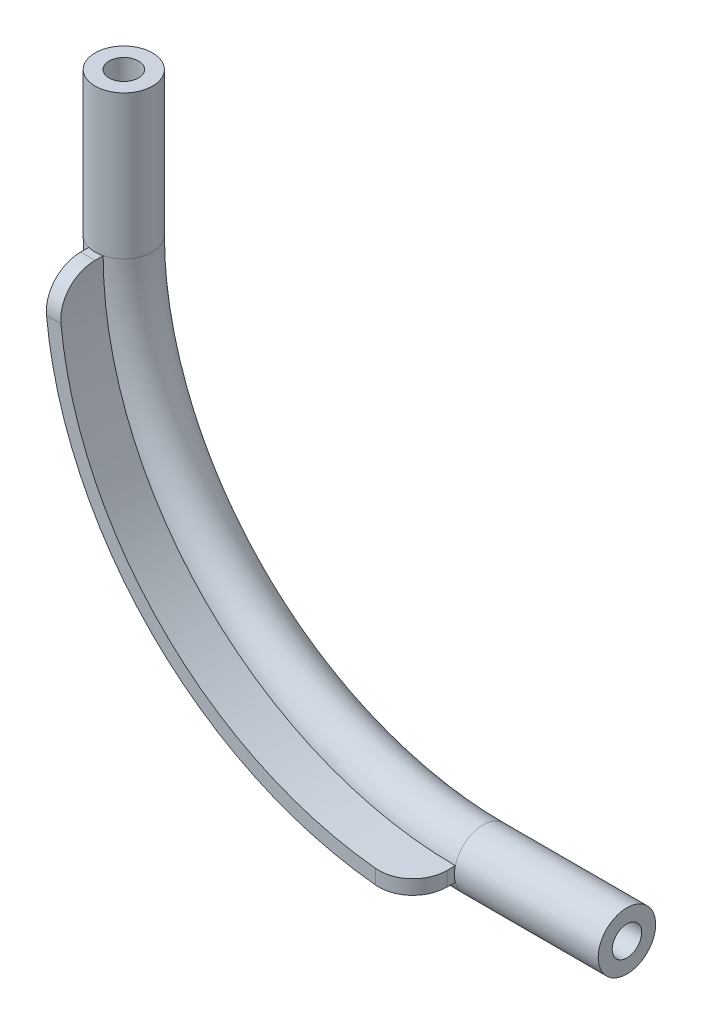
SolidWorks part; units mm, degrees
ref_plane "前基準面" through (0, 0, 0) normal (0, 0, 1) x (1, 0, 0)
ref_plane "上基準面" through (0, 0, 0) normal (0, 1, 0) x (1, 0, 0)
ref_plane "右基準面" through (0, 0, 0) normal (1, 0, 0) x (0, 0, -1)
sketch "草圖4" plane through (0, 0, 0) normal (0, 1, 0) x (1, 0, 0)
  line L0 (0, 3.4749) -> (0, -3.49) construction
  line L1 (0, -3.8307) -> (0, 3.8307) construction
  line L2 (-55, 0) -> (55, 0) construction
  circle A0 centre (-50, 0) radius 4
  dimension "D1" = 50
  dimension "D2" = 8
revolve "旋轉1" add sketch "草圖4" angle 90 about L0
sketch "草圖5" plane through (0, 0, 0) normal (1, 0, 0) x (0, 0, -1)
  circle A0 centre (0, -50) radius 4 construction
  circle A1 centre (0, -50) radius 4
  circle A2 centre (0, -50) radius 2.05
  dimension "D1" = 4.1
extrude "填料-伸長4" add sketch "草圖5" along normal blind 20 contours A1 | A2
sketch "草圖6" plane through (0, 0, 0) normal (0, 1, 0) x (1, 0, 0)
  circle A0 centre (-50, 0) radius 4 construction
  circle A1 centre (-50, 0) radius 4
  circle A2 centre (-50, 0) radius 2.05
  dimension "D1" = 4.1
extrude "填料-伸長5" add sketch "草圖6" along normal blind 20
sketch "草圖7" plane through (0, 0, 0) normal (0, 0, 1) x (1, 0, 0)
  line L0 (10.0499, -50) -> (-4.9615, -50) construction
  line L2 (-3.7268, -49) -> (6.7893, -49) construction
  line L3 (-3.7268, -51) -> (6.7893, -51) construction
  line L4 (-49, 0) -> (-51, 0)
  line L5 (0, -49) -> (0, -51)
  arc A0 (-49, 0) -> (0, -49) centre (0, 0) ccw
  arc A1 (-51, 0) -> (0, -51) centre (0, 0) ccw
  dimension "D1" = 1
extrude "填料-伸長6" add sketch "草圖7" along normal blind 10
fillet "圓角1" radius 5 2 edges at (0, -50, 10) (-50, 0, 10)
